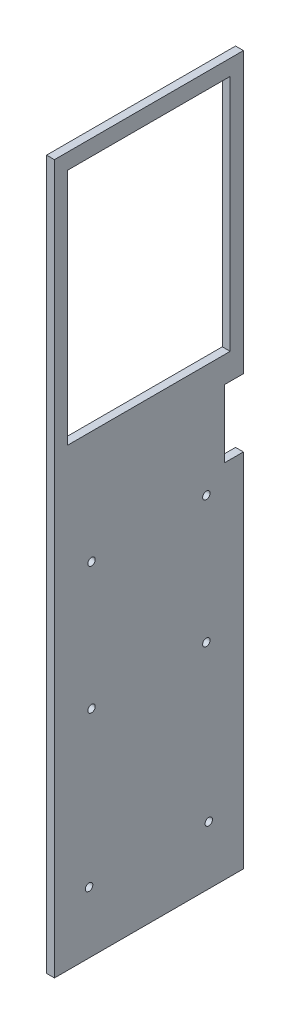
SolidWorks part; units mm, degrees
ref_plane "Front Plane" through (0, 0, 0) normal (0, 0, 1) x (1, 0, 0)
ref_plane "Top Plane" through (0, 0, 0) normal (0, 1, 0) x (1, 0, 0)
ref_plane "Right Plane" through (0, 0, 0) normal (1, 0, 0) x (0, 0, -1)
sketch "Sketch1" plane through (0, 0, 0) normal (1, 0, 0) x (0, 0, -1)
  line L1 (0, 0) -> (76.2, 0)
  line L2 (0, 0) -> (0, 285.75)
  line L3 (0, 285.75) -> (76.2, 285.75)
  line L4 (76.2, 0) -> (76.2, 285.75)
  dimension "D1" = 76.2
  dimension "D2" = 285.75
extrude "Boss-Extrude1" add sketch "Sketch1" along normal blind 3.175
ref_plane "Plane1" through (0, 0, -38.1) normal (0, 0, -1) x (-1, 0, 0)
sketch "Sketch2" plane through (0, 0, 0) normal (-1, 0, 0) x (0, 0, 1)
  line L1 (-70.866, 183.388) -> (-5.334, 183.388)
  line L2 (-70.866, 183.388) -> (-70.866, 279.4)
  line L3 (-70.866, 279.4) -> (-5.334, 279.4)
  line L4 (-5.334, 183.388) -> (-5.334, 279.4)
  line L6 (-76.2, 285.75) -> (0, 285.75) construction
  point P6 (-38.1, 285.75)
  point P7 (-38.1, 279.4)
  dimension "D1" = 96.012
  dimension "D2" = 65.532
  dimension "D3" = 6.35
extrude "Cut-Extrude1" cut sketch "Sketch2" against normal up to next
sketch "Sketch3" plane through (0, 0, 0) normal (-1, 0, 0) x (0, 0, 1)
  line L0 (-76.2, 0) -> (-76.2, 285.75) construction
  line L1 (-76.2, 145.605) -> (-68.58, 145.605)
  line L2 (-76.2, 145.605) -> (-76.2, 172.905)
  line L3 (-76.2, 172.905) -> (-68.58, 172.905)
  line L4 (-68.58, 145.605) -> (-68.58, 172.905)
  line L5 (-64.23, 172.905) -> (-60.03, 172.905) construction
  line L6 (-60.03, 145.605) -> (-57.53, 145.605) construction
  line L7 (-68.58, 159.005) -> (-68.58, 156.505) construction
extrude "Cut-Extrude2" cut sketch "Sketch3" against normal up to next
hole_wizard "Ø3.0mm Dowel Hole1" positions "Sketch4" profile "Sketch5" hole size "Ø3.0" standard "ANSI Metric" end condition up to next
sketch "Sketch4" plane through (0, 0, 0) normal (-1, 0, 0) x (0, 0, 1)
  point P0 (-62.23, 23.495)
  point P3 (-13.97, 24.765)
  point P6 (-14.95, 86.605)
  point P9 (-61.25, 86.605)
  point P12 (-61.25, 137.905)
  point P15 (-14.95, 137.905)
sketch "Sketch5" plane through (0, 23.495, -62.23) normal (0, 1, 0) x (0, 0, 1)
  line L0 (0, 0) -> (0, 3.175)
  line L1 (0, 3.175) -> (1.5, 3.175)
  line L2 (1.5, 3.175) -> (1.5, 0)
  line L5 (1.5, 0) -> (0, 0)
  line L11 (0, -6.35) -> (0, 107.95) construction
  dimension "Thru Hole Dia." = 3
  dimension "Thru Hole Depth" = 3.175
